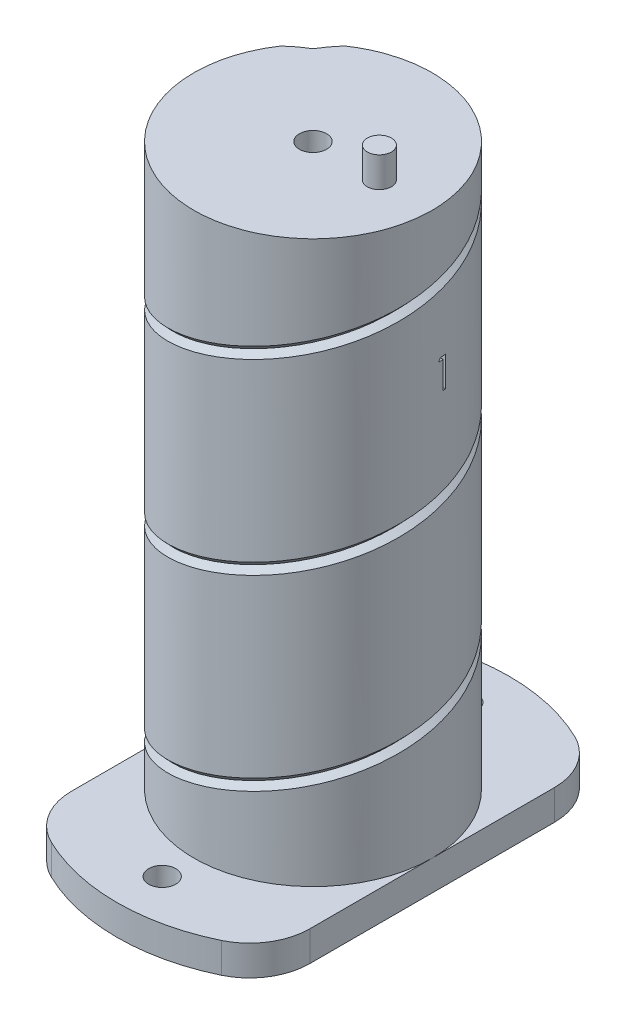
SolidWorks part; units mm, degrees
ref_plane "Front Plane" through (0, 0, 0) normal (0, 0, 1) x (1, 0, 0)
ref_plane "Top Plane" through (0, 0, 0) normal (0, 1, 0) x (1, 0, 0)
ref_plane "Right Plane" through (0, 0, 0) normal (1, 0, 0) x (0, 0, -1)
sketch "Sketch1" plane through (0, 0, 0) normal (0, 1, 0) x (1, 0, 0)
  line L0 (-19.75, 0) -> (19.75, 0) construction
  circle A0 centre (0, 0) radius 19.75
  dimension "D1" = 39.5
curve "Helix - Antenna Guide" pitch 31 height 93 radius 19.75 centre (0, 0, 0) axis (0, 1, 0) start towards (0, 0, 1)
extrude "Extrude - Main Body" add sketch "Sketch1<2>" along normal blind 93
sketch "Sketch1<2>" plane through (0, 0, 0) normal (0, 1, 0) x (1, 0, 0) same geometry as "Sketch1"
ref_point "Point2"
ref_point "Point1"
ref_plane "Plane1" through (-13.9654, 0, -13.9654) normal (-0.686, 0.2424, 0.686) x (-0.7276, -0.2285, -0.6468)
sketch "Sketch15" plane through (-13.9654, 0, -13.9654) normal (-0.686, 0.2424, 0.686) x (-0.7276, -0.2285, -0.6468)
  line L4 (0, 0) -> (0.2165, 0.8934)
  line L5 (0.2165, 0.8934) -> (-0.8934, 0.2165)
  line L8 (0, 0) -> (-0.2165, -0.8934)
  line L9 (-0.2165, -0.8934) -> (-0.8934, 0.2165)
  point P7 (-0.5549, -0.3384)
  dimension "D1" = 0.65
  dimension "D2" = 90
sweep "Cut - Antenna Wire Guide" cut profiles "Sketch15" path "Helix - Antenna Guide" align with end faces yes
sketch "Sketch26" plane through (0, 93, 0) normal (0, 1, 0) x (1, 0, 0)
  point P0 (0, 0)
hole_wizard "#8 Clearance Hole1" positions "Sketch27" profile "Sketch28" hole size "#8" standard "ANSI Inch" end condition through all
sketch "Sketch27" plane through (0, 93, 0) normal (0, 1, 0) x (1, 0, 0)
  point P0 (0, 0)
sketch "Sketch28" plane through (0, 93, 0) normal (1, 0, 0) x (0, 0, 1)
  line L0 (0, 0) -> (0, 94.4693)
  line L1 (0, 94.4693) -> (2.2479, 94.4693)
  line L2 (2.2479, 94.4693) -> (2.2479, 0)
  line L5 (2.2479, 0) -> (0, 0)
  line L11 (0, -6.35) -> (0, 107.95) construction
  dimension "Thru Hole Dia." = 4.4958
  dimension "Thru Hole Depth" = 94.4693
sketch "Sketch29" plane through (0, 93, 0) normal (0, 1, 0) x (1, 0, 0)
  circle A0 centre (11, 0) radius 2
  dimension "D2" = 4
  dimension "D1" = 11
extrude "Extruded Peg" add sketch "Sketch29" along normal blind 5
sketch "Sketch30" plane through (0, 0, 0) normal (0, -1, 0) x (1, 0, 0)
  circle A4 centre (0, 0) radius 32.5
  point P0 (0, 0)
  dimension "D1" = 65
extrude "Boss-Extrude5" add sketch "Sketch30" along normal blind 5
sketch "Sketch34" plane through (0, 0, 0) normal (0, 1, 0) x (1, 0, 0)
  line L0 (0, 0) -> (0, 25) construction
  point P0 (0, 25)
  point P4 (25, 0)
  point P6 (0, -25)
  point P7 (-25, 0)
  dimension "D1" = 25
  dimension "D2" = 4
hole_wizard "#8 Clearance Hole2" positions "Sketch35" profile "Sketch36" hole size "#8" standard "ANSI Inch" end condition through all
sketch "Sketch35" plane through (0, 0, 0) normal (0, 1, 0) x (1, 0, 0)
  point P0 (25, 0)
  point P3 (0, 25)
  point P6 (-25, 0)
  point P9 (0, -25)
sketch "Sketch36" plane through (25, 0, 0) normal (1, 0, 0) x (0, 0, 1)
  line L0 (0, 0) -> (0, 5)
  line L1 (0, 5) -> (2.2479, 5)
  line L2 (2.2479, 5) -> (2.2479, 0)
  line L5 (2.2479, 0) -> (0, 0)
  line L11 (0, -6.35) -> (0, 107.95) construction
  dimension "Thru Hole Dia." = 4.4958
  dimension "Thru Hole Depth" = 5
sketch "Sketch37" plane through (0, 0, 0) normal (0, 1, 0) x (1, 0, 0)
  line L1 (19.75, 25.8106) -> (19.75, -25.8106)
  line L3 (-19.75, 25.8106) -> (-19.75, -25.8106)
  circle A1 centre (0, 0) radius 32.5 construction
  arc A2 (19.75, 25.8106) -> (19.75, -25.8106) centre (0, 0) cw
  arc A3 (-19.75, 25.8106) -> (-19.75, -25.8106) centre (0, 0) ccw
extrude "Cut-Extrude4" cut sketch "Sketch37" against normal up to surface (5 mm away) up to face at (25, -5, 2.2479)
sketch "Sketch38" plane through (19.75, 0, 0) normal (1, 0, 0) x (0, 0, -1)
  text T0 "1" font "Century Gothic" height 5
extrude "Cut-Extrude5" cut sketch "Sketch38" against normal blind 2 draft 1
fillet "Fillet1" radius 10 4 edges at (-19.75, -2.5, -25.8106) (-19.75, -2.5, 25.8106) (19.75, -2.5, -25.8106) (19.75, -2.5, 25.8106)
sketch "Sketch39" plane through (0, -5, 0) normal (0, -1, 0) x (1, 0, 0)
  line L0 (-19.75, 20.2778) -> (-19.75, -20.2778) construction
  circle A0 centre (-14.75, -14.2778) radius 1
  point P6 (-35.851, -101.3277)
  dimension "D3" = 2
  dimension "D1" = 5
  dimension "D2" = 6
extrude "Cut-Extrude6" cut sketch "Sketch39" against normal up to surface (5 mm away) up to face at (-2.5477, 0, -15.892)
equation "\"pegD\"=10"
equation "\"pegHoleD\"=0.5"
equation "\"pegHoleOffset\"=0.5"
